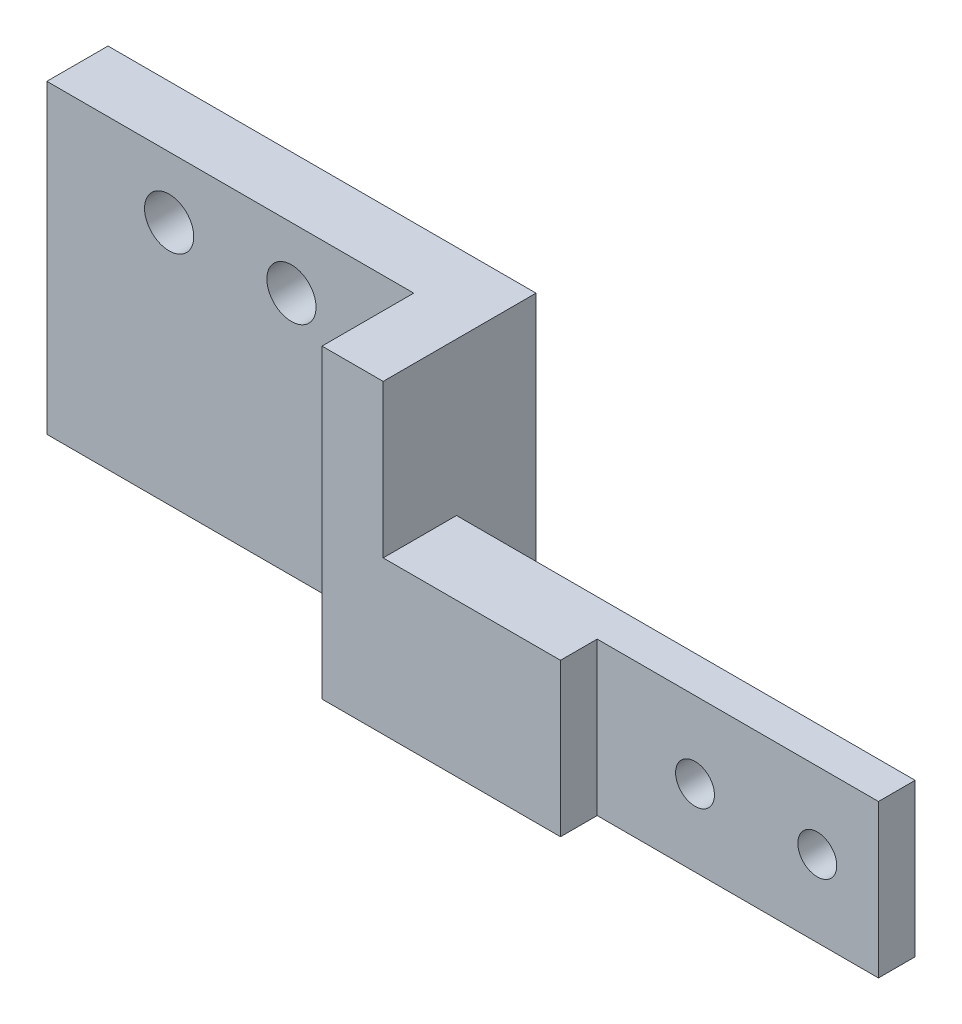
SolidWorks part; units mm, degrees
ref_plane "Front Plane" through (0, 0, 0) normal (0, 0, 1) x (1, 0, 0)
ref_plane "Top Plane" through (0, 0, 0) normal (0, 1, 0) x (1, 0, 0)
ref_plane "Right Plane" through (0, 0, 0) normal (1, 0, 0) x (0, 0, -1)
sketch "Sketch1" plane through (0, 0, 0) normal (0, 1, 0) x (1, 0, 0)
  line L1 (-46.0375, -7.9375) -> (46.0375, -7.9375)
  line L2 (-46.0375, -7.9375) -> (-46.0375, 7.9375)
  line L3 (-46.0375, 7.9375) -> (46.0375, 7.9375)
  line L4 (46.0375, -7.9375) -> (46.0375, 7.9375)
  line L5 (-46.0375, -7.9375) -> (46.0375, 7.9375) construction
  line L6 (-46.0375, 7.9375) -> (46.0375, -7.9375) construction
  point P0 (0, 0)
  dimension "D1" = 92.075
  dimension "D2" = 15.875
extrude "Boss-Extrude1" add sketch "Sketch1" along normal mid plane 31.75
sketch "Sketch2" plane through (0, 0, 7.9375) normal (0, 0, 1) x (1, 0, 0)
  line L0 (-46.0375, 15.875) -> (-46.0375, -15.875) construction
  line L1 (46.0375, 15.875) -> (-1.5875, 15.875)
  line L2 (46.0375, 15.875) -> (46.0375, 0)
  line L3 (46.0375, 0) -> (-1.5875, 0)
  line L4 (-1.5875, 15.875) -> (-1.5875, 0)
  dimension "D1" = 44.45
  dimension "D2" = 15.875
extrude "Cut-Extrude1" cut sketch "Sketch2" against normal up to next
hole_wizard "#10 (0.1935) Diameter Hole1" positions "Sketch4" profile "Sketch3" hole size "#10" standard "ANSI Inch" end condition up to next
sketch "Sketch4" plane through (0, 0, 7.9375) normal (0, 0, 1) x (1, 0, 0)
  line L0 (-46.0375, 15.875) -> (-46.0375, -15.875) construction
  line L1 (-1.5875, 0) -> (46.0375, 0) construction
  point P0 (-33.3375, 9.525)
  point P2 (-20.6375, 9.525)
  dimension "D1" = 12.7
  dimension "D2" = 12.7
  dimension "D3" = 9.525
sketch "Sketch3" plane through (-33.3375, 9.525, 7.9375) normal (1, 0, 0) x (0, -1, 0)
  line L0 (0, 0) -> (0, 15.875)
  line L1 (0, 15.875) -> (2.5527, 15.875)
  line L2 (2.5527, 15.875) -> (2.5527, 0)
  line L5 (2.5527, 0) -> (0, 0)
  line L11 (0, -6.35) -> (0, 107.95) construction
  dimension "Thru Hole Dia." = 5.1054
  dimension "Thru Hole Depth" = 15.875
sketch "Sketch5" plane through (0, 0, 0) normal (0, 1, 0) x (1, 0, 0)
  line L0 (-1.5875, 7.9375) -> (-1.5875, -7.9375) construction
  line L1 (46.0375, 7.9375) -> (-1.5875, 7.9375)
  line L2 (46.0375, 7.9375) -> (46.0375, -0.3175)
  line L3 (46.0375, -0.3175) -> (-1.5875, -0.3175)
  line L4 (-1.5875, 7.9375) -> (-1.5875, -0.3175)
  line L5 (-1.5875, -7.9375) -> (46.0375, -7.9375) construction
  dimension "D1" = 7.62
extrude "Cut-Extrude2" cut sketch "Sketch5" against normal up to next
sketch "Sketch6" plane through (0, 0, 0) normal (0, 1, 0) x (1, 0, 0)
  line L1 (46.0375, -7.9375) -> (-1.5875, -7.9375)
  line L2 (46.0375, -7.9375) -> (46.0375, -4.1275)
  line L3 (46.0375, -4.1275) -> (-1.5875, -4.1275)
  line L4 (-1.5875, -7.9375) -> (-1.5875, -4.1275)
  line L5 (-1.5875, 7.9375) -> (-1.5875, -7.9375) construction
  dimension "D1" = 3.81
extrude "Cut-Extrude3" cut sketch "Sketch6" against normal up to next
sketch "Sketch7" plane through (0, 15.875, 0) normal (0, 1, 0) x (1, 0, 0)
  line L0 (-1.5875, 7.9375) -> (-1.5875, -7.9375) construction
  line L1 (-46.0375, -7.9375) -> (-7.9375, -7.9375)
  line L2 (-46.0375, -7.9375) -> (-46.0375, 1.5875)
  line L3 (-46.0375, 1.5875) -> (-7.9375, 1.5875)
  line L4 (-7.9375, -7.9375) -> (-7.9375, 1.5875)
  line L5 (-1.5875, 7.9375) -> (-46.0375, 7.9375) construction
  dimension "D1" = 6.35
  dimension "D2" = 6.35
extrude "Cut-Extrude4" cut sketch "Sketch7" against normal through all
sketch "Sketch8" plane through (0, 15.875, 0) normal (0, 1, 0) x (1, 0, 0)
  line L0 (-7.9375, -7.9375) -> (-7.9375, 1.5875) construction
  line L1 (-1.5875, -7.9375) -> (-7.9375, -7.9375)
  line L2 (-1.5875, -7.9375) -> (-1.5875, -4.1275)
  line L3 (-1.5875, -4.1275) -> (-7.9375, -4.1275)
  line L4 (-7.9375, -7.9375) -> (-7.9375, -4.1275)
  line L5 (46.0375, -4.1275) -> (-1.5875, -4.1275) construction
extrude "Cut-Extrude5" cut sketch "Sketch8" against normal through all
hole_wizard "#10-32 Tapped Hole1" positions "Sketch10" profile "Sketch9" tap size "#10-32" standard "ANSI Inch" end condition up to next
sketch "Sketch10" plane through (0, 0, 4.1275) normal (0, 0, 1) x (1, 0, 0)
  line L0 (46.0375, -15.875) -> (-7.9375, -15.875) construction
  line L1 (46.0375, -15.875) -> (46.0375, 0) construction
  point P0 (39.6875, -7.9375)
  point P2 (26.9875, -7.9375)
  dimension "D1" = 7.9375
  dimension "D2" = 6.35
  dimension "D3" = 12.7
sketch "Sketch9" plane through (39.6875, -7.9375, 4.1275) normal (1, 0, 0) x (0, -1, 0)
  line L0 (0, 0) -> (0, 3.81)
  line L1 (0, 3.81) -> (2.0193, 3.81)
  line L2 (2.0193, 3.81) -> (2.0193, 0)
  line L5 (2.0193, 0) -> (0, 0)
  line L11 (0, -6.35) -> (0, 107.95) construction
  dimension "Thru Tap Drill Dia." = 4.0386
  dimension "Thru Tap Drill Depth" = 3.81
cosmetic thread "Hole Thread1" parameters "D2"=4.826
cosmetic thread "Hole Thread2" parameters "D2"=4.826
sketch "Sketch11" plane through (0, 0, 4.1275) normal (0, 0, 1) x (1, 0, 0)
  line L0 (-7.9375, -15.875) -> (-7.9375, 15.875) construction
  line L1 (-7.9375, 0) -> (16.8275, 0)
  line L2 (-7.9375, 0) -> (-7.9375, -15.875)
  line L3 (-7.9375, -15.875) -> (16.8275, -15.875)
  line L4 (16.8275, 0) -> (16.8275, -15.875)
  line L5 (46.0375, -15.875) -> (-7.9375, -15.875) construction
  line L6 (46.0375, -15.875) -> (46.0375, 0) construction
  dimension "D1" = 29.21
extrude "Boss-Extrude2" add sketch "Sketch11" along normal blind 3.81
sketch "Sketch12" plane through (0, 0, 4.1275) normal (0, 0, 1) x (1, 0, 0)
  line L1 (-7.9375, 15.875) -> (-1.5875, 15.875)
  line L2 (-7.9375, 15.875) -> (-7.9375, 0)
  line L3 (-7.9375, 0) -> (-1.5875, 0)
  line L4 (-1.5875, 15.875) -> (-1.5875, 0)
extrude "Boss-Extrude3" add sketch "Sketch12" along normal blind 3.81
